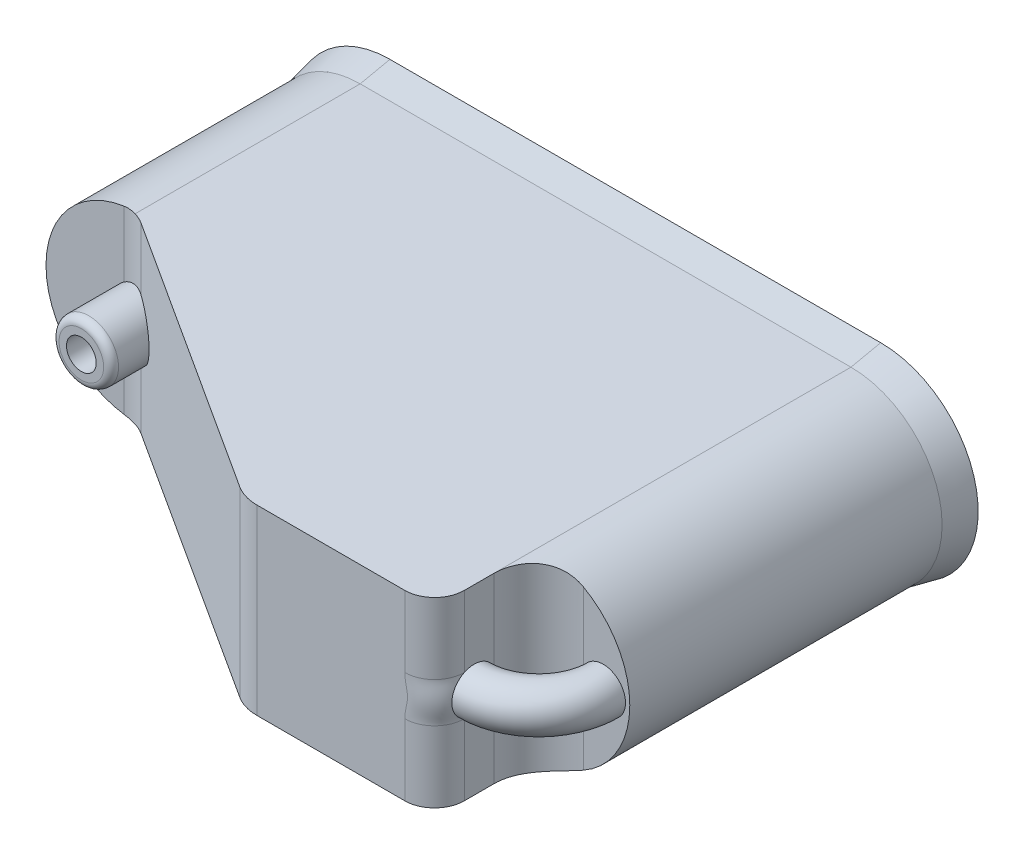
SolidWorks part; units mm, degrees
ref_plane "Front Plane" through (0, 0, 0) normal (0, 0, 1) x (1, 0, 0)
ref_plane "Top Plane" through (0, 0, 0) normal (0, 1, 0) x (1, 0, 0)
ref_plane "Right Plane" through (0, 0, 0) normal (1, 0, 0) x (0, 0, -1)
sketch "Sketch5" plane through (0, 0, 0) normal (0, 1, 0) x (1, 0, 0)
  line L0 (-165, 0) -> (165, 0) construction
  line L1 (-165, 59) -> (165, 59)
  line L2 (-165, 59) -> (-165, -59)
  line L3 (-165, -59) -> (165, -59)
  line L4 (165, 59) -> (165, -59)
  line L5 (-165, 59) -> (165, -59) construction
  line L6 (-165, -59) -> (165, 59) construction
  line L7 (-165, 65.5291) -> (165, 65.5291)
  line L8 (-165, -65.5291) -> (165, -65.5291)
  arc A0 (-165, 65.5291) -> (-165, -65.5291) centre (-165, 0) ccw
  arc A1 (165, -65.5291) -> (165, 65.5291) centre (165, 0) ccw
  point P0 (0, 0)
  point P8 (0, 0)
  dimension "D1" = 118
  dimension "D2" = 330
extrude "Boss-Extrude5" add sketch "Sketch5" along normal blind 20 draft 12 contours A0 L8 A1 L7
sketch "Sketch6" plane through (0, 20, 0) normal (0, 1, 0) x (1, 0, 0)
  line L0 (165, 61.2779) -> (165, -61.2779)
  line L1 (165, 61.2779) -> (36.681, 61.2779)
  line L2 (165, -61.2779) -> (36.681, -61.2779)
  line L3 (36.681, 61.2779) -> (36.681, -61.2779)
extrude "Boss-Extrude6" add sketch "Sketch6" along normal blind 280
sketch "Sketch7" plane through (0, 0, 61.2779) normal (0, 0, 1) x (1, 0, 0)
  line L0 (36.681, 300) -> (36.681, 20)
  line L1 (36.681, 20) -> (-165, 20)
  line L2 (-165, 20) -> (-165, 170)
  line L3 (-165, 170) -> (36.681, 300)
  dimension "D1" = 150
extrude "Boss-Extrude7" add sketch "Sketch7" against normal up to surface (122.5559 mm away) up to face at (100.8405, 160, -61.2779)
sketch "Sketch8" plane through (0, 20, 0) normal (0, 1, 0) x (1, 0, 0)
  line L0 (-165, 61.2779) -> (-165, -61.2779)
  arc A0 (-165, 61.2779) -> (-165, -61.2779) centre (-165, 0) ccw
extrude "Boss-Extrude8" add sketch "Sketch8" along normal blind 150
sketch "Sketch10" plane through (0, 0, 0) normal (0, -1, 0) x (1, 0, 0)
  line L0 (0, 0) -> (162.5, 0)
  circle A0 centre (162.5, 0) radius 10
  dimension "D2" = 20
  dimension "D1" = 162.5
extrude "Boss-Extrude9" add sketch "Sketch10" along normal blind 35 contours A0
sketch "Sketch11" plane through (0, 0, 0) normal (0, -1, 0) x (1, 0, 0)
  line L0 (0, 0) -> (-162.5, 0)
  circle A0 centre (-162.5, 0) radius 10
  dimension "D2" = 20
  dimension "D1" = 162.5
sketch "Sketch13" plane through (0, 0, 0) normal (0, -1, 0) x (1, 0, 0)
  line L0 (-181.9351, 0) -> (-143.0649, 0) construction
  line L1 (0, 0) -> (-162.5, 0) construction
  line L2 (-181.9351, 24.0728) -> (-143.0649, 24.0728)
  line L3 (-181.9351, -24.0728) -> (-143.0649, -24.0728)
  arc A0 (-181.9351, 24.0728) -> (-181.9351, -24.0728) centre (-181.9351, 0) ccw
  arc A1 (-143.0649, -24.0728) -> (-143.0649, 24.0728) centre (-143.0649, 0) ccw
  point P5 (-162.5, 0)
extrude "Boss-Extrude11" add sketch "Sketch13" along normal blind 40
sketch "Sketch14" plane through (0, 0, 0) normal (0, -1, 0) x (1, 0, 0)
  circle A0 centre (-162.5, 0) radius 20
  dimension "D1" = 40
extrude "Boss-Extrude12" add sketch "Sketch14" against normal blind 210
extrude "Cut-Extrude3" cut sketch "Sketch11" against normal up to surface and the other way up to surface contours A0 up to face at (-162.5, 210, -20) other way up to face at (-162.5, -40, 0)
sketch "Sketch15" plane through (0, 20, 0) normal (0, 1, 0) x (1, 0, 0)
  line L0 (165, 61.2779) -> (165, -61.2779)
  arc A0 (165, -61.2779) -> (165, 61.2779) centre (165, 0) ccw
extrude "Boss-Extrude13" add sketch "Sketch15" along normal blind 210
sketch "Sketch16" plane through (165, 0, 0) normal (1, 0, 0) x (0, 0, -1)
  circle A0 centre (0, 273.3956) radius 15
  dimension "D1" = 30
sketch "Sketch17" plane through (0, 0, 61.2779) normal (0, 0, 1) x (1, 0, 0)
  line L0 (165, 258.3956) -> (165, 288.3956) construction
  line L1 (226.2779, 230) -> (165, 230) construction
  arc A0 (165, 273.3956) -> (208.3956, 230) centre (165, 230) cw
sketch "Sketch18" plane through (0, 230, 0) normal (0, 1, 0) x (1, 0, 0)
sweep "Sweep1" add profiles "Sketch16" path "Sketch17"
fillet "Fillet6" radius 30 1 edges at (36.681, 300, 0)
fillet "Fillet7" radius 30 2 edges at (-165, 170, -40.5605) (-165, 170, 40.5605)
fillet "Fillet8" radius 30 1 edges at (165, 230, 0)
fillet "Fillet9" radius 20 1 edges at (165, 300, 0)
fillet "Fillet10" radius 5 1 edges at (-162.5, 210, -20)
sketch "Sketch20" plane through (0, 0, 0) normal (0, -1, 0) x (1, 0, 0)
  point P0 (162.5, 0)
move or copy body "Body-Move/Copy1" bodies to move or copy 117 copy no translate (-162.5, 0, 0)
move or copy body "Body-Move/Copy2" bodies to move or copy 118 copy no rotation origin (0, 0, 0) rotation axis (1, 0, 0) rotation angle 90
sketch "Sketch24" plane through (0, -61.2779, 0) normal (0, -1, 0) x (1, 0, 0)
  text T0 "NGOC_HOAN" font "Century Gothic" height 35
